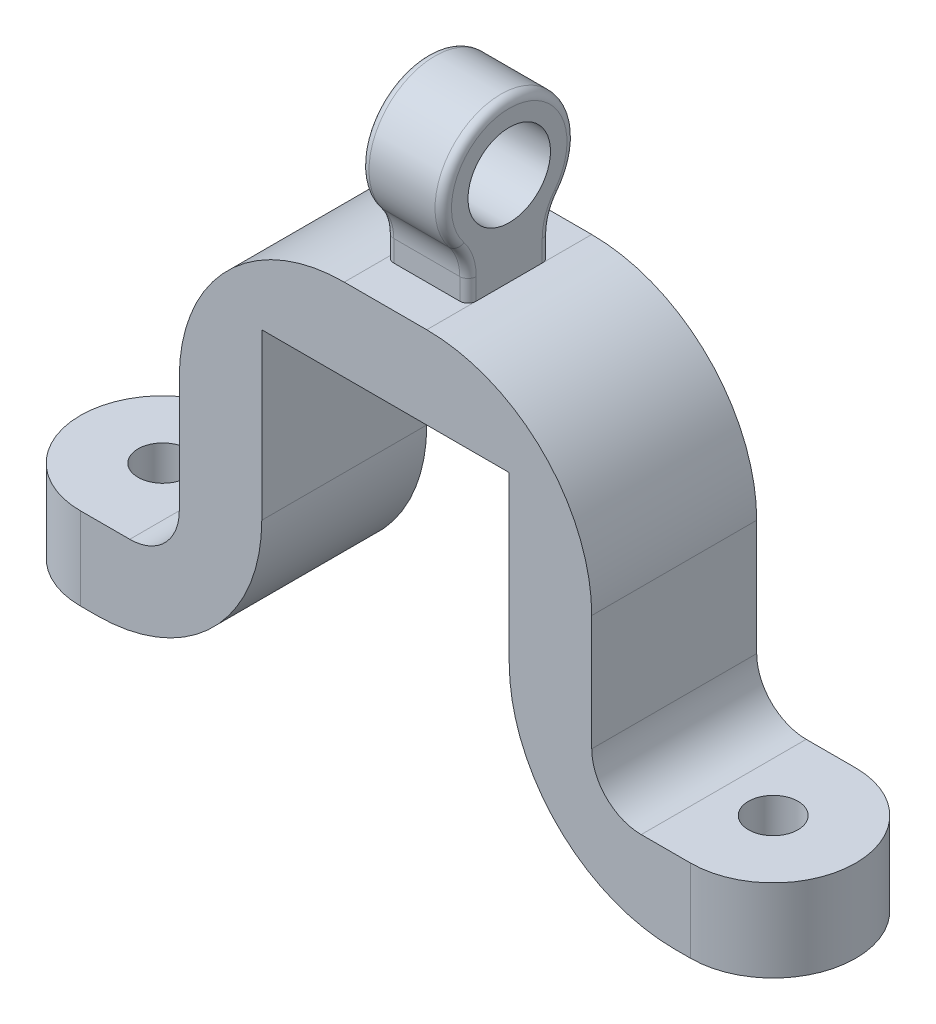
SolidWorks part; units mm, degrees
ref_plane "Plan de face" through (0, 0, 0) normal (0, 0, 1) x (1, 0, 0)
ref_plane "Plan de dessus" through (0, 0, 0) normal (0, 1, 0) x (1, 0, 0)
ref_plane "Plan de droite" through (0, 0, 0) normal (1, 0, 0) x (0, 0, -1)
sketch "Esquisse1" plane through (0, 0, 0) normal (0, 0, 1) x (1, 0, 0)
  line L0 (0, 0) -> (16, 0)
  line L1 (16, 0) -> (16, 20)
  line L2 (16, 20) -> (31, 20)
  line L3 (31, 20) -> (31, 0)
  line L4 (31, 0) -> (47, 0)
  line L5 (0, 5) -> (11, 5)
  line L6 (11, 5) -> (11, 25)
  line L7 (11, 25) -> (36, 25)
  line L8 (36, 25) -> (36, 5)
  line L9 (36, 5) -> (47, 5)
  line L10 (0, 5) -> (0, 0)
  line L11 (47, 5) -> (47, 0)
  dimension "D1" = 20
  dimension "D2" = 16
  dimension "D3" = 16
  dimension "D4" = 15
  dimension "D5" = 5
extrude "Boss.-Extru.1" add sketch "Esquisse1" along normal blind 10
fillet "Congé1" 2 edges at (0, 2.5, 10) (0, 2.5, 0) type full round first side face at (23.5, 9.1667, 10) second side face at (23.5, 9.1667, 0) middle face at (0, 2.5, 5)
fillet "Congé2" 2 edges at (47, 2.5, 10) (47, 2.5, 0) type full round first side face at (24.3333, 9.1667, 10) second side face at (24.3333, 9.1667, 0) middle face at (47, 2.5, 5)
fillet "Congé3" radius 10 2 edges at (31, 0, 5) (16, 0, 5)
fillet "Congé4" radius 10 2 edges at (36, 25, 5) (11, 25, 5)
fillet "Congé6" radius 3 1 edges at (11, 5, 5) type face fillet first side face at (6.75, 5, 5) second side face at (11, 10, 5)
fillet "Congé7" radius 3 1 edges at (36, 5, 5) type face fillet first side face at (40.25, 5, 5) second side face at (36, 10, 5)
sketch "Esquisse2" plane through (0, 5, 0) normal (0, 1, 0) x (1, 0, 0)
  circle A0 centre (5, -5) radius 1.5
  circle A1 centre (42, -5) radius 1.5
  dimension "D1" = 3
  dimension "D2" = 3
extrude "Enlèv. mat.-Extru.1" cut sketch "Esquisse2" against normal blind 10
sketch "Esquisse3" plane through (0, 0, 0) normal (1, 0, 0) x (0, 0, -1)
  line L0 (-5, 29.1151) -> (-5, 20.8509) construction
  line L2 (-10, 25) -> (-10, 15) construction
  line L3 (-7.5, 25) -> (-7.5, 27.5)
  line L4 (-10, 25) -> (0, 25) construction
  line L5 (-2.5, 25) -> (-2.5, 27.5)
  line L6 (-7.5, 27.5) -> (-2.5, 27.5)
  line L7 (-7.5, 25) -> (-2.5, 25)
  point P3 (-5, 24.983)
  dimension "D1" = 5
  dimension "D2" = 2.5
  dimension "D3" = 2.5
extrude "Boss.-Extru.2" add sketch "Esquisse3" along normal blind 5 from offset 21
sketch "Esquisse5" plane through (26, 0, 0) normal (1, 0, 0) x (0, 0, -1)
  line L0 (-7.5, 27.5) -> (-2.5, 27.5)
  arc A0 (-7.5, 27.5) -> (-2.5, 27.5) centre (-5, 30.6225) cw
  circle A1 centre (-5, 30.6225) radius 2.5
  dimension "D1" = 5
extrude "Boss.-Extru.3" add sketch "Esquisse5" against normal blind 5
fillet "Congé8" radius 3 1 edges at (23.5, 27.5, 7.5) type face fillet first side face at (23.5, 26.25, 7.5) second side face at (23.5, 31.0612, 5)
fillet "Congé9" radius 3 1 edges at (23.5, 27.5, 2.5) type face fillet first side face at (23.5, 26.25, 2.5) second side face at (23.5, 31.2102, 4.9325)
fillet "Congé14" radius 0.5 10 edges at (26, 25.6462, 2.5) (26, 27.2744, 2.3347) (26, 25.6462, 7.5) (26, 27.2744, 7.6653) (21, 25.6462, 2.5) (21, 27.2744, 2.3347) (21, 25.6462, 7.5) (21, 27.2744, 7.6653) (26, 34.6225, 5) (21, 34.6225, 5)
